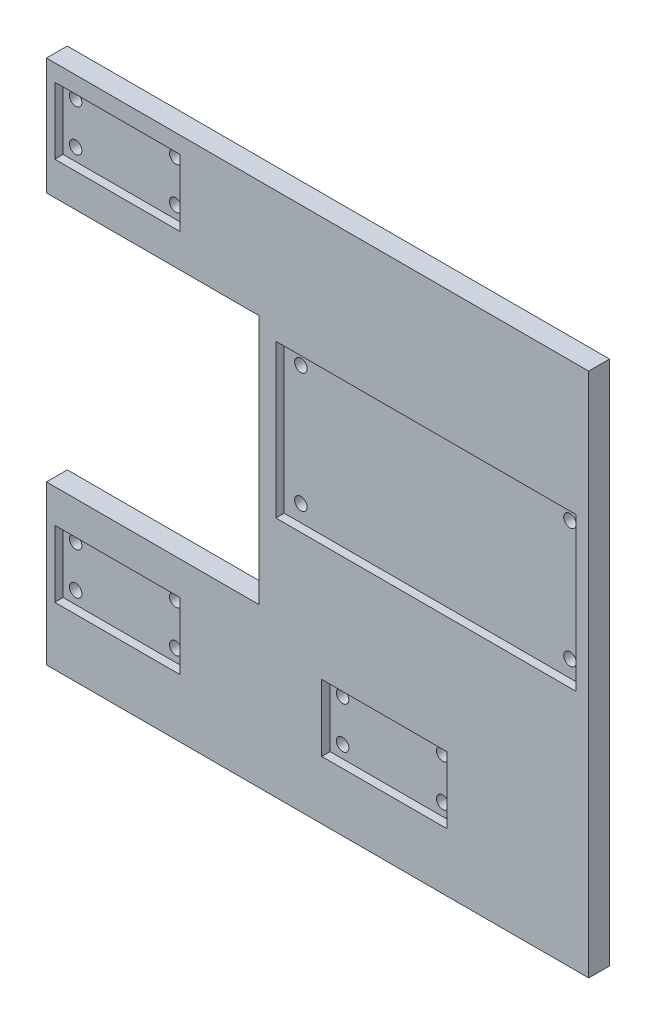
SolidWorks part; units mm, degrees
ref_plane "前视基准面" through (0, 0, 0) normal (0, 0, 1) x (1, 0, 0)
ref_plane "上视基准面" through (0, 0, 0) normal (0, 1, 0) x (1, 0, 0)
ref_plane "右视基准面" through (0, 0, 0) normal (1, 0, 0) x (0, 0, -1)
other "Configuration Table"
sketch "草图1" plane through (0, 0, 0) normal (0, 0, 1) x (1, 0, 0)
  line L0 (0, 0) -> (0, 30)
  line L1 (0, 30) -> (120, 30)
  line L2 (120, 30) -> (120, -96)
  line L3 (120, -96) -> (0, -96)
  line L4 (0, -96) -> (0, -56)
  line L5 (0, -56) -> (45, -56)
  line L6 (45, -56) -> (45, 0)
  line L7 (45, 0) -> (0, 0)
  dimension "D1" = 30
  dimension "D2" = 56
  dimension "D3" = 40
  dimension "D4" = 45
  dimension "D5" = 120
  dimension "D6" = 120
extrude "凸台-拉伸2" add sketch "草图1" along normal blind 5
sketch "草图3" plane through (0, 0, 5) normal (0, 0, 1) x (1, 0, 0)
  line L0 (0, 0) -> (0, 10)
  line L1 (0, 30) -> (0, 0) construction
  line L2 (0, 10) -> (17, 10)
  line L3 (-955, -28) -> (49045, -28) construction
  line L4 (2, 1.95) -> (32, 1.95)
  line L5 (2, 1.95) -> (2, 18.05)
  line L6 (2, 18.05) -> (32, 18.05)
  line L7 (32, 1.95) -> (32, 18.05)
  line L8 (2, 1.95) -> (32, 18.05) construction
  line L9 (2, 18.05) -> (32, 1.95) construction
  line L10 (45, 0) -> (45, -56) construction
  line L11 (2, -74.05) -> (32, -57.95) construction
  line L12 (2, -57.95) -> (32, -74.05) construction
  line L13 (32, -57.95) -> (32, -74.05)
  line L14 (2, -74.05) -> (32, -74.05)
  line L15 (2, -57.95) -> (2, -74.05)
  line L16 (2, -57.95) -> (32, -57.95)
  line L17 (0, -66) -> (17, -66)
  line L18 (0, -56) -> (0, -66)
  point P15 (45, -28)
  dimension "D1" = 10
  dimension "D2" = 17
  dimension "D3" = 16.1
  dimension "D4" = 30
extrude "切除-拉伸1" cut sketch "草图3" against normal blind 2 contours L4 L7 L6 L5 | L16 L15 L14 L13 region at (2.3405, 5.975, 5) region at (31.6595, -66, 5)
sketch "草图4" plane through (0, 0, 3) normal (0, 0, 1) x (1, 0, 0)
  line L0 (2, 18.05) -> (17, 18.05)
  line L5 (2, 18.05) -> (32, 18.05) construction
  line L6 (17, 18.05) -> (17, 10)
  line L7 (-998, 10) -> (49002, 10) construction
  line L8 (2, 2) -> (32, 2)
  line L9 (2, 2) -> (2, 18)
  line L10 (2, 18) -> (32, 18)
  line L11 (32, 2) -> (32, 18)
  line L12 (2, 2) -> (32, 18) construction
  line L13 (2, 18) -> (32, 2) construction
  line L14 (2, 18) -> (5, 18)
  line L15 (2, 18) -> (2, 15)
  line L16 (2, 15) -> (5, 15)
  line L17 (5, 18) -> (5, 15)
  line L18 (-955, -28) -> (49045, -28) construction
  line L19 (45, 0) -> (45, -56) construction
  circle A0 centre (5, 15) radius 1.55
  circle A1 centre (29, 15) radius 1.55
  circle A2 centre (29, 5) radius 1.55
  circle A3 centre (5, 5) radius 1.55
  circle A4 centre (5, -61) radius 1.55
  circle A5 centre (29, -61) radius 1.55
  circle A6 centre (29, -71) radius 1.55
  circle A7 centre (5, -71) radius 1.55
  point P20 (2, 10)
  point P29 (45, -28)
  dimension "D5" = 3.1
  dimension "D1" = 30
  dimension "D2" = 16
  dimension "D3" = 3
  dimension "D4" = 3
extrude "切除-拉伸2" cut sketch "草图4" against normal up to next contours A1 | A2 | L16 A0 L17 | L17 A0 L16 | A3 | A4 | A7 | A5 | A6 region at (4.3422, 15.6578, 3) region at (5.2193, 14.7807, 3) region at (29, 15, 3) region at (29, 5, 3) region at (5, 5, 3) region at (5, -61, 3) region at (29, -61, 3) region at (29, -71, 3) region at (5, -71, 3)
sketch "草图5" plane through (0, 0, 5) normal (0, 0, 1) x (1, 0, 0)
  line L0 (17, -74.05) -> (17, 18.05) construction
  line L1 (2, -74.05) -> (32, -74.05) construction
  line L2 (2, 18.05) -> (32, 18.05) construction
  line L3 (17, -74.05) -> (17, -85.05) construction
  line L4 (17, -85.05) -> (17, -96) construction
  line L5 (0, -96) -> (120, -96) construction
  line L6 (17, -96) -> (77, -96)
  line L7 (45, -56) -> (0, -56) construction
  line L8 (17, -56) -> (49, -56)
  line L9 (17, -56) -> (17, 0)
  line L10 (17, 0) -> (49, 0)
  line L11 (49, -56) -> (49, 0)
  dimension "D1" = 11
  dimension "D2" = 60
  dimension "D3" = 32
extrude "切除-拉伸3" cut sketch "草图5" against normal up to next contours L8 L11 L10 L9 region at (33, -28, 5)
sketch "草图7" plane through (0, 0, 5) normal (0, 0, 1) x (1, 0, 0)
  line L0 (49, -56) -> (59, -56)
  line L2 (59, -56) -> (99.5, -56)
  line L3 (59, -56) -> (59, -15.5)
  line L4 (59, -15.5) -> (99.5, -15.5)
  line L5 (99.5, -56) -> (99.5, -15.5)
  dimension "D1" = 10
  dimension "D2" = 40.5
  dimension "D3" = 40.5
extrude "凸台-拉伸4" add sketch "草图7" along normal blind 2 contours L2 L5 L4 L3 region at (79.25, -35.75, 5)
sketch "草图8" plane through (0, 0, 5) normal (0, 0, 1) x (1, 0, 0)
  line L0 (17, -998.05) -> (17, 49001.95) construction
  line L1 (2, 1.95) -> (32, 1.95) construction
  line L2 (59, -56) -> (69.5, -56)
  line L3 (59, -56) -> (99.5, -56) construction
  line L4 (69.5, -1056) -> (69.5, 48944) construction
  line L5 (69.5, -56) -> (69.5, -60.5)
  line L6 (69.5, -60.5) -> (69.5, -70.5)
  line L8 (54.25, -78.75) -> (84.75, -78.75)
  line L9 (54.25, -78.75) -> (54.25, -62.25)
  line L10 (54.25, -62.25) -> (84.75, -62.25)
  line L11 (84.75, -78.75) -> (84.75, -62.25)
  line L12 (54.25, -78.75) -> (84.75, -62.25) construction
  line L13 (54.25, -62.25) -> (84.75, -78.75) construction
  point P5 (17, 1.95)
  dimension "D1" = 10.5
  dimension "D2" = 4.5
  dimension "D3" = 10
  dimension "D4" = 30.5
  dimension "D5" = 16.5
extrude "切除-拉伸4" cut sketch "草图8" against normal blind 2 contours L8 L11 L10 L9 region at (54.5968, -70.5, 5)
sketch "草图9" plane through (0, 0, 3) normal (0, 0, 1) x (1, 0, 0)
  line L0 (-945.75, -70.5) -> (49054.25, -70.5) construction
  line L1 (54.25, -62.25) -> (57.5, -62.25)
  line L2 (54.25, -62.25) -> (54.25, -65.5)
  line L3 (54.25, -65.5) -> (57.5, -65.5)
  line L4 (57.5, -62.25) -> (57.5, -65.5)
  line L5 (54.25, -78.75) -> (54.25, -62.25) construction
  line L6 (69.5, -1062.25) -> (69.5, 48937.75) construction
  line L7 (54.25, -62.25) -> (84.75, -62.25) construction
  circle A0 centre (57.5, -65.5) radius 1.55
  circle A1 centre (81.5, -65.5) radius 1.55
  circle A2 centre (81.5, -75.5) radius 1.55
  circle A3 centre (57.5, -75.5) radius 1.55
  point P11 (54.25, -70.5)
  point P16 (69.5, -62.25)
  dimension "D3" = 3.1
  dimension "D1" = 3.25
  dimension "D2" = 3.25
extrude "切除-拉伸6" cut sketch "草图9" against normal through all contours A1 | A0 | A3 | A2 region at (81.5, -65.5, 3)
sketch "草图10" plane through (0, 0, 7) normal (0, 0, 1) x (1, 0, 0)
  line L1 (59, -56) -> (119, -56)
  line L2 (59, -56) -> (59, -11)
  line L3 (59, -11) -> (119, -11)
  line L4 (119, -56) -> (119, -11)
  dimension "D1" = 60
  dimension "D2" = 45
extrude "凸台-拉伸5" add sketch "草图10" against normal blind 2
sketch "草图11" plane through (0, 0, 5) normal (0, 0, 1) x (1, 0, 0)
  line L1 (59, -11) -> (119, -11)
  line L2 (59, -11) -> (59, -56)
  line L3 (59, -56) -> (119, -56)
  line L4 (119, -11) -> (119, -56)
extrude "切除-拉伸8" cut sketch "草图11" along normal blind 2
sketch "草图12" plane through (0, 0, 5) normal (0, 0, 1) x (1, 0, 0)
  line L1 (2, 1.95) -> (32, 1.95)
  line L2 (2, 1.95) -> (2, 18.05)
  line L3 (2, 18.05) -> (32, 18.05)
  line L4 (32, 1.95) -> (32, 18.05)
  line L5 (2, -57.95) -> (32, -57.95)
  line L6 (2, -57.95) -> (2, -74.05)
  line L7 (2, -74.05) -> (32, -74.05)
  line L8 (32, -57.95) -> (32, -74.05)
  line L9 (54.25, -62.25) -> (84.75, -62.25)
  line L10 (54.25, -62.25) -> (54.25, -78.75)
  line L11 (54.25, -78.75) -> (84.75, -78.75)
  line L12 (84.75, -62.25) -> (84.75, -78.75)
extrude "凸台-拉伸6" add sketch "草图12" against normal blind 5
sketch "草图13" plane through (0, 0, 5) normal (0, 0, 1) x (1, 0, 0)
  line L0 (0, 0) -> (0, 10)
  line L1 (0, 30) -> (0, 0) construction
  line L2 (0, 10) -> (2, 10)
  line L3 (-951, -28) -> (49049, -28) construction
  line L4 (2, 10) -> (32, 10)
  line L5 (2, 10) -> (2, 26)
  line L6 (2, 26) -> (32, 26)
  line L7 (32, 10) -> (32, 26)
  line L8 (49, -56) -> (49, 0) construction
  line L9 (32, -66) -> (32, -82)
  line L10 (2, -82) -> (32, -82)
  line L11 (2, -66) -> (2, -82)
  line L12 (2, -66) -> (32, -66)
  line L13 (-998, 18) -> (49002, 18) construction
  line L14 (2, 26) -> (5, 26)
  line L15 (2, 26) -> (2, 23)
  line L16 (2, 23) -> (5, 23)
  line L17 (5, 26) -> (5, 23)
  line L19 (17, -974) -> (17, 49026) construction
  circle A0 centre (5, 23) radius 1.5
  circle A1 centre (29, 23) radius 1.5
  circle A2 centre (29, 13) radius 1.5
  circle A3 centre (5, 13) radius 1.5
  circle A4 centre (5, -69) radius 1.5
  circle A5 centre (29, -69) radius 1.5
  circle A6 centre (29, -79) radius 1.5
  circle A7 centre (5, -79) radius 1.5
  point P14 (49, -28)
  point P25 (2, 18)
  point P30 (17, 26)
  dimension "D7" = 3
  dimension "D1" = 10
  dimension "D2" = 2
  dimension "D3" = 16
  dimension "D4" = 30
  dimension "D5" = 3
  dimension "D6" = 3
extrude "切除-拉伸10" cut sketch "草图13" against normal blind 5 contours A4 | A7 | A2 | A1 | A3 | A6 | A5 | A0 region at (29, 23, 5) region at (29, 13, 5) region at (5, 13, 5) region at (5, -69, 5) region at (5, -79, 5)
sketch "草图14" plane through (0, 0, 5) normal (0, 0, 1) x (1, 0, 0)
  line L1 (2, 26) -> (32, 26)
  line L2 (2, 26) -> (2, 10)
  line L3 (2, 10) -> (32, 10)
  line L4 (32, 26) -> (32, 10)
  line L5 (2, -66) -> (32, -66)
  line L6 (2, -66) -> (2, -82)
  line L7 (2, -82) -> (32, -82)
  line L8 (32, -66) -> (32, -82)
extrude "切除-拉伸11" cut sketch "草图14" against normal blind 2
sketch "草图15" plane through (0, 0, 5) normal (0, 0, 1) x (1, 0, 0)
  line L0 (-2, 2) -> (-2, -58)
  line L1 (0, 0) -> (49, 0)
  line L2 (0, 0) -> (0, -56)
  line L3 (0, -56) -> (49, -56)
  line L4 (49, 0) -> (49, -56)
  line L5 (-2, -58) -> (51, -58)
  line L6 (51, 2) -> (51, -58)
  line L7 (-2, 2) -> (51, 2)
  dimension "D1" = 2
extrude "切除-拉伸12" cut sketch "草图15" against normal blind 5
sketch "草图16" plane through (0, 0, 5) normal (0, 0, 1) x (1, 0, 0)
  line L0 (51, -58) -> (61, -58)
  line L1 (61, -58) -> (61, -66)
  line L3 (61, -66) -> (91, -66)
  line L4 (61, -66) -> (61, -82)
  line L5 (61, -82) -> (91, -82)
  line L6 (91, -66) -> (91, -82)
  dimension "D1" = 10
  dimension "D2" = 30
  dimension "D3" = 16
extrude "切除-拉伸13" cut sketch "草图16" against normal blind 2 contours L6 L3 L4 L5 region at (76, -74, 5)
sketch "草图17" plane through (0, 0, 3) normal (0, 0, 1) x (1, 0, 0)
  line L0 (-939, -74) -> (49061, -74) construction
  line L1 (61, -66) -> (64, -66)
  line L2 (61, -66) -> (61, -69)
  line L3 (61, -69) -> (64, -69)
  line L4 (64, -66) -> (64, -69)
  line L5 (61, -66) -> (61, -82) construction
  line L6 (76, -1066) -> (76, 48934) construction
  line L7 (61, -66) -> (91, -66) construction
  circle A0 centre (64, -69) radius 1.5
  circle A1 centre (88, -69) radius 1.5
  circle A2 centre (88, -79) radius 1.5
  circle A3 centre (64, -79) radius 1.5
  point P11 (61, -74)
  point P16 (76, -66)
  dimension "D3" = 3
  dimension "D1" = 3
  dimension "D2" = 3
extrude "切除-拉伸15" cut sketch "草图17" against normal through all contours A1 | A2 | A3 | A0 region at (88, -69, 3) region at (88, -79, 3) region at (64, -79, 3)
sketch "草图18" plane through (0, 0, 5) normal (0, 0, 1) x (1, 0, 0)
  line L0 (76, -66) -> (76, -46)
  line L1 (61, -66) -> (91, -66) construction
  line L2 (76, -46) -> (106, -46)
  line L3 (76, -46) -> (66, -46)
  line L4 (66, -46) -> (50, -46)
  line L5 (66, -46) -> (106, -46)
  line L6 (66, -46) -> (66, -6)
  line L7 (66, -6) -> (106, -6)
  line L8 (106, -46) -> (106, -6)
  line L9 (106, -46) -> (122, -46)
  line L11 (120, 30) -> (130, 30)
  line L12 (120, 30) -> (120, -96)
  line L13 (120, -96) -> (130, -96)
  line L14 (130, 30) -> (130, -96)
  line M11 (120, -96) -> (120, 30)
  dimension "D1" = 20
  dimension "D2" = 30
  dimension "D3" = 10
  dimension "D4" = 40
  dimension "D5" = 16
  dimension "D6" = 16
  dimension "D7" = 10
extrude "凸台-拉伸7" add sketch "草图18" against normal blind 5 contours L14 L11 L13 M11 region at (125, -33, 5)
sketch "草图19" plane through (0, 0, 5) normal (0, 0, 1) x (1, 0, 0)
  line L1 (61, -66) -> (91, -66)
  line L2 (61, -66) -> (61, -82)
  line L3 (61, -82) -> (91, -82)
  line L4 (91, -66) -> (91, -82)
extrude "凸台-拉伸8" add sketch "草图19" against normal blind 5
sketch "草图20" plane through (0, 0, 5) normal (0, 0, 1) x (1, 0, 0)
  line L0 (32, -74) -> (72, -74)
  line L1 (32, -66) -> (32, -82) construction
  line L2 (51, -58) -> (71, -58)
  line L3 (71, -58) -> (71, -38)
  line L4 (71, -38) -> (81, -38)
  line L5 (71, -38) -> (111, -38)
  line L6 (71, -38) -> (71, 2)
  line L7 (71, 2) -> (111, 2)
  line L8 (111, -38) -> (111, 2)
  line L9 (81, -38) -> (81, -74)
  line L10 (71, -38) -> (55, -38)
  line L11 (111, -38) -> (127, -38)
  line L13 (55, -38) -> (127, -38)
  line L14 (55, -38) -> (55, -1.3)
  line L15 (55, -1.3) -> (127, -1.3)
  line L16 (127, -38) -> (127, -1.3)
  line L17 (66, -82) -> (96, -82)
  line L18 (66, -82) -> (66, -66)
  line L19 (66, -66) -> (96, -66)
  line L20 (96, -82) -> (96, -66)
  line L21 (66, -82) -> (96, -66) construction
  line L22 (66, -66) -> (96, -82) construction
  dimension "D1" = 40
  dimension "D2" = 20
  dimension "D3" = 20
  dimension "D4" = 40
  dimension "D5" = 40
  dimension "D6" = 10
  dimension "D7" = 16
  dimension "D8" = 16
  dimension "D9" = 36.7
  dimension "D10" = 16
  dimension "D11" = 30
extrude "切除-拉伸17" cut sketch "草图20" against normal blind 2 contours L15 L14 L10 L6 | L15 L6 L4 L5 L8 | L11 L16 L15 L8 | L17 L20 L19 L18 region at (91, -19.65, 5) region at (63, -19.65, 5) region at (88.5, -66.34, 5) region at (119, -19.65, 5)
sketch "草图21" plane through (0, 0, 3) normal (0, 0, 1) x (1, 0, 0)
  line L0 (-945, -19.65) -> (49055, -19.65) construction
  line L1 (55, -1.3) -> (59, -1.3)
  line L2 (55, -1.3) -> (55, -5.3)
  line L3 (55, -5.3) -> (59, -5.3)
  line L4 (59, -1.3) -> (59, -5.3)
  line L5 (55, -38) -> (55, -1.3) construction
  line L6 (91, -1001.3) -> (91, 48998.7) construction
  line L7 (55, -1.3) -> (127, -1.3) construction
  line L8 (-934, -74) -> (49066, -74) construction
  line L9 (66, -66) -> (69, -66)
  line L10 (66, -66) -> (66, -69)
  line L11 (66, -69) -> (69, -69)
  line L12 (69, -66) -> (69, -69)
  line L13 (66, -82) -> (66, -66) construction
  line L14 (81, -1066) -> (81, 48934) construction
  line L15 (66, -66) -> (96, -66) construction
  circle A0 centre (59, -5.3) radius 1.5
  circle A1 centre (123, -5.3) radius 1.5
  circle A2 centre (123, -34) radius 1.5
  circle A3 centre (59, -34) radius 1.5
  circle A4 centre (69, -69) radius 1.5
  circle A5 centre (93, -69) radius 1.5
  circle A6 centre (93, -79) radius 1.5
  circle A7 centre (69, -79) radius 1.5
  point P11 (55, -19.65)
  point P16 (91, -1.3)
  point P33 (66, -74)
  point P38 (81, -66)
  dimension "D3" = 3
  dimension "D6" = 3
  dimension "D1" = 4
  dimension "D2" = 4
  dimension "D4" = 3
  dimension "D5" = 3
extrude "切除-拉伸18" cut sketch "草图21" against normal through all contours L3 A0 L4 | L4 A0 L3 | A3 | A2 | A1 | A5 | A7 | A6 | A4 region at (59.2122, -5.5122, 3) region at (58.3634, -4.6634, 3) region at (123, -5.3, 3) region at (123, -34, 3) region at (59, -34, 3) region at (93, -69, 3) region at (69, -79, 3)
sketch "草图22" plane through (0, 0, 3) normal (0, 0, 1) x (1, 0, 0)
  circle A0 centre (123, -5.3) radius 1.5
  circle A1 centre (123, -34) radius 1.5
extrude "凸台-拉伸10" add sketch "草图22" against normal blind 3
sketch "草图23" plane through (0, 0, 3) normal (0, 0, 1) x (1, 0, 0)
  line L1 (127, -1.3) -> (123.5, -1.3)
  line L2 (127, -1.3) -> (127, -5.3)
  line L3 (127, -5.3) -> (123.5, -5.3)
  line L4 (123.5, -1.3) -> (123.5, -5.3)
  line L5 (127, -38) -> (123.5, -38)
  line L6 (127, -38) -> (127, -34)
  line L7 (127, -34) -> (123.5, -34)
  line L8 (123.5, -38) -> (123.5, -34)
  circle A0 centre (123.5, -5.3) radius 1.5
  circle A1 centre (123.5, -34) radius 1.5
  dimension "D3" = 3
  dimension "D6" = 3
  dimension "D1" = 3.5
  dimension "D2" = 4
  dimension "D4" = 3.5
  dimension "D5" = 4
extrude "切除-拉伸19" cut sketch "草图23" against normal through all contours L4 A0 L3 | L3 A0 L4 | A1 region at (124.1366, -4.6634, 3) region at (123.2878, -5.5122, 3)
